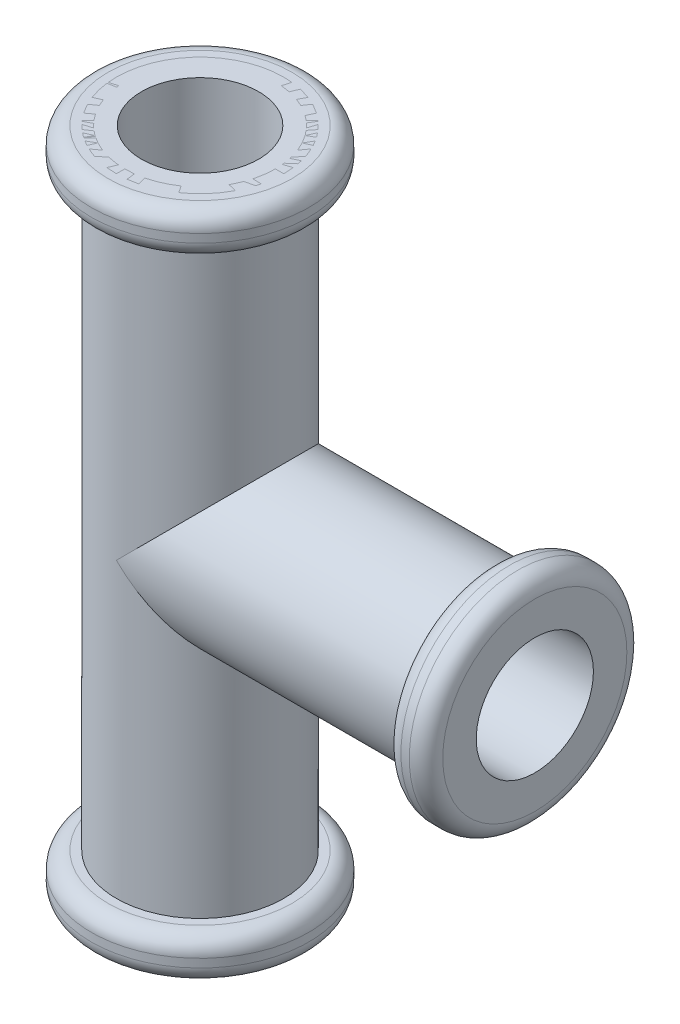
SolidWorks part; units mm, degrees
ref_plane "前视基准面" through (0, 0, 0) normal (0, 0, 1) x (1, 0, 0)
ref_plane "上视基准面" through (0, 0, 0) normal (0, 1, 0) x (1, 0, 0)
ref_plane "右视基准面" through (0, 0, 0) normal (1, 0, 0) x (0, 0, -1)
sketch "草图1" plane through (0, 0, 0) normal (0, 1, 0) x (1, 0, 0)
  circle A0 centre (0, 0) radius 10
  dimension "D1" = 20
extrude "凸台-拉伸1" add sketch "草图1" along normal mid plane 80
shell "抽壳1" thickness 3 removed face at (0, -40, 10) removed face at (0, 40, 10)
ref_plane "基准面1" through (40, 0, 0) normal (1, 0, 0) x (0, 0, -1)
sketch "草图2" plane through (40, 0, 0) normal (1, 0, 0) x (0, 0, -1)
  circle A0 centre (0, 0) radius 10
  dimension "D1" = 20
extrude "凸台-拉伸2" add sketch "草图2" against normal up to surface (40 mm away) up to face at (0, 40, 10)
sketch "草图3" plane through (40, 0, 0) normal (1, 0, 0) x (0, 0, -1)
  circle A0 centre (0, 0) radius 7
  dimension "D1" = 14
extrude "切除-拉伸1" cut sketch "草图3" against normal up to surface (40 mm away) up to face at (0, 40, 7)
sketch "草图5" plane through (0, 40, 0) normal (0, 1, 0) x (1, 0, 0)
  circle A2 centre (0, 0) radius 13
  circle A3 centre (0, 0) radius 13
  dimension "D1" = 3
extrude "拉伸-薄壁2" add sketch "草图5" against normal blind 5 separate body thin thin type one direction reverse wall 4
sketch "草图6" plane through (40, 0, 0) normal (1, 0, 0) x (0, 0, -1)
  circle A2 centre (0, 0) radius 13
  circle A3 centre (0, 0) radius 13
  dimension "D1" = 3
extrude "拉伸-薄壁3" add sketch "草图6" against normal blind 5 thin thin type one direction reverse wall 4
sketch "草图7" plane through (0, -40, 0) normal (0, -1, 0) x (1, 0, 0)
  circle A2 centre (0, 0) radius 13
  circle A3 centre (0, 0) radius 13
  dimension "D1" = 3
extrude "拉伸-薄壁4" add sketch "草图7" against normal blind 5 thin thin type one direction reverse wall 4
fillet "圆角1" radius 2 4 edges at (0, -40, -13) (0, -35, -13) (35, 0, -13) (40, 0, -13)
fillet "圆角2" radius 2 3 edges at (0, 35, 13) (9, 35, 0) (0, 40, 13)
